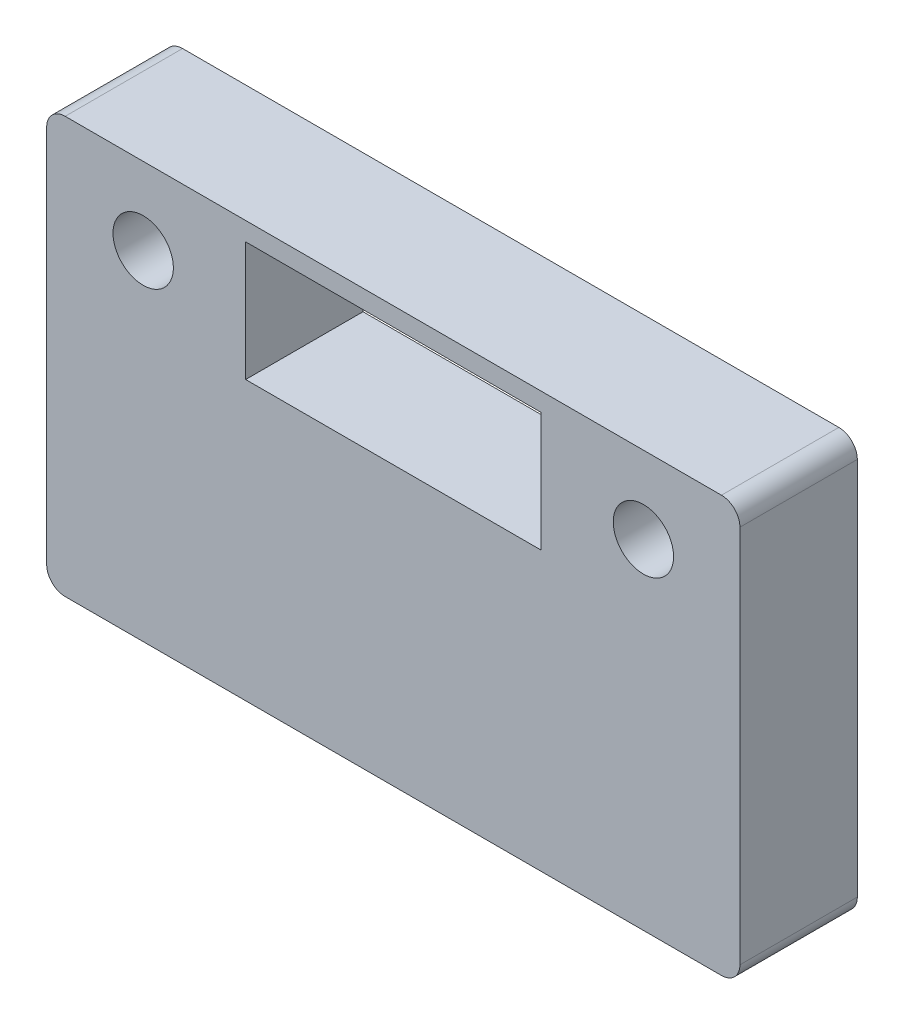
SolidWorks part; units mm, degrees
ref_plane "Front Plane" through (0, 0, 0) normal (0, 0, 1) x (1, 0, 0)
ref_plane "Top Plane" through (0, 0, 0) normal (0, 1, 0) x (1, 0, 0)
ref_plane "Right Plane" through (0, 0, 0) normal (1, 0, 0) x (0, 0, -1)
sketch "Sketch1" plane through (0, 0, 0) normal (0, 0, 1) x (1, 0, 0)
  line L0 (37.5, -2) -> (53.475, -2)
  line L1 (0, 0) -> (75, 0)
  line L2 (0, 0) -> (0, -45)
  line L3 (0, -45) -> (75, -45)
  line L4 (75, 0) -> (75, -45)
  line L5 (53.475, -2) -> (53.475, -14.9)
  line L6 (53.475, -14.9) -> (21.525, -14.9)
  line L7 (21.525, -14.9) -> (21.525, -2)
  line L8 (21.525, -2) -> (37.5, -2)
  dimension "D1" = 75
  dimension "D2" = 45
  dimension "D3" = 12.9
  dimension "D4" = 2
  dimension "D5" = 31.95
  dimension "D6" = 37.5
extrude "Boss-Extrude1" add sketch "Sketch1" along normal blind 12.7
sketch "Sketch2" plane through (0, 0, 0) normal (0, 0, -1) x (-1, 0, 0)
  line L0 (-75, -8.35) -> (-64.56, -8.35)
  line L1 (-75, -45) -> (-75, 0) construction
  line L2 (0, -8.35) -> (-10.44, -8.35)
  line L3 (0, 0) -> (0, -45) construction
  dimension "D1" = 10.44
  dimension "D2" = 10.44
hole_wizard "CSK for 1/4 Flat Head Machine Screw2" positions "Sketch5" profile "Sketch6" countersink size "1/4" standard "ANSI Inch" end condition through all
sketch "Sketch5" plane through (0, 0, 0) normal (0, 0, -1) x (-1, 0, 0)
  point P0 (-64.56, -8.35)
  point P3 (-10.44, -8.35)
sketch "Sketch6" plane through (64.56, -8.35, 0) normal (1, 0, 0) x (0, 1, 0)
  line L0 (0, 0) -> (0, 12.7)
  line L1 (0, 12.7) -> (3.2639, 12.7)
  line L2 (3.2639, 12.7) -> (3.2639, 3.6524)
  line L3 (3.2639, 3.6524) -> (6.4389, 0)
  line L5 (6.4389, 0) -> (0, 0)
  line L6 (-3.2639, 3.6524) -> (-6.4389, 0) construction
  line L11 (0, -6.35) -> (0, 107.95) construction
  dimension "Thru Hole Dia." = 6.5278
  dimension "Thru Hole Depth" = 12.7
  dimension "Near C'Sink Dia." = 12.8778
  dimension "Near C'Sink Angle" = 82
fillet "Fillet1" radius 2 2 edges at (0, 0, 6.35) (0, -45, 6.35)
fillet "Fillet2" radius 2 2 edges at (75, -45, 6.35) (75, 0, 6.35)
